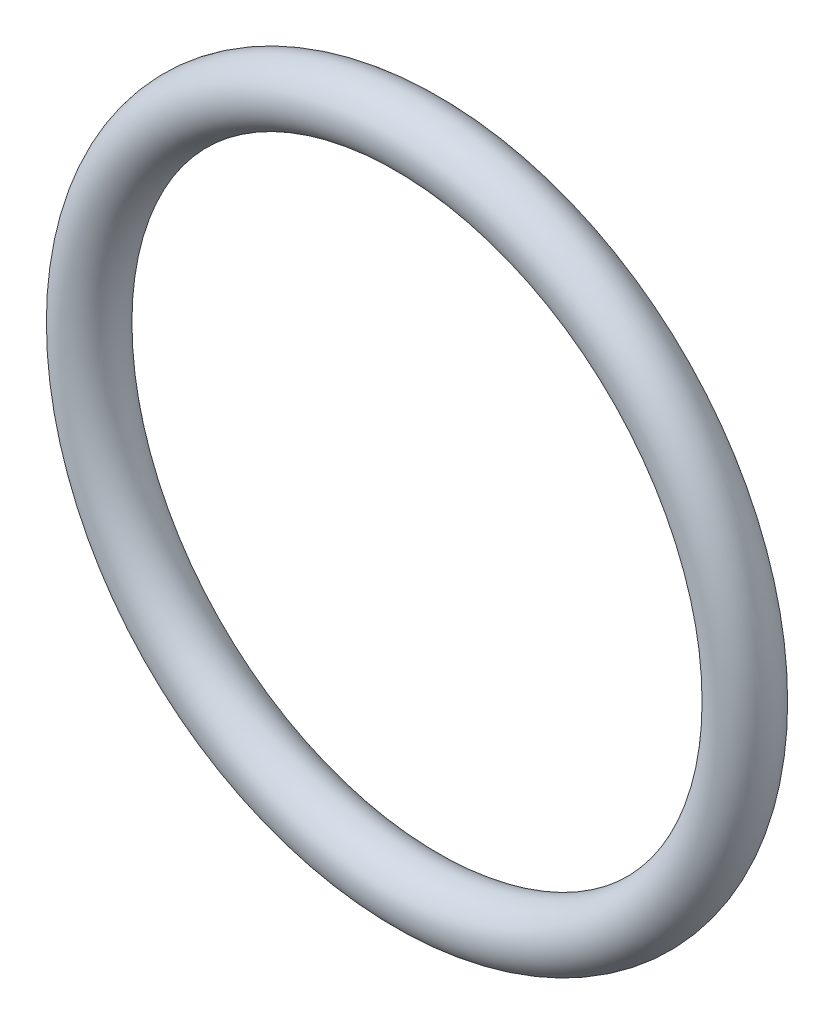
SolidWorks part; units mm, degrees
ref_plane "Front Plane" through (0, 0, 0) normal (0, 0, 1) x (1, 0, 0)
ref_plane "Top Plane" through (0, 0, 0) normal (0, 1, 0) x (1, 0, 0)
ref_plane "Right Plane" through (0, 0, 0) normal (1, 0, 0) x (0, 0, -1)
sketch "Sketch3" plane through (0, 0, 0) normal (0, 1, 0) x (1, 0, 0)
  line L0 (0, 1.5) -> (0, -1.5) construction
  circle A0 centre (-16.25, 0) radius 1.5
  point P6 (0, 0)
  dimension "D1" = 3
  dimension "D2" = 16.25
  dimension "D3" = 3
revolve "Revolve1" add sketch "Sketch3" angle 360 about L0
ref_axis "Axis1" through (0, 0, -1.65) along (0, 0, 1)
ref_plane "Plane1" through (0, -17.75, 0) normal (0, 1, 0) x (1, 0, 0)
